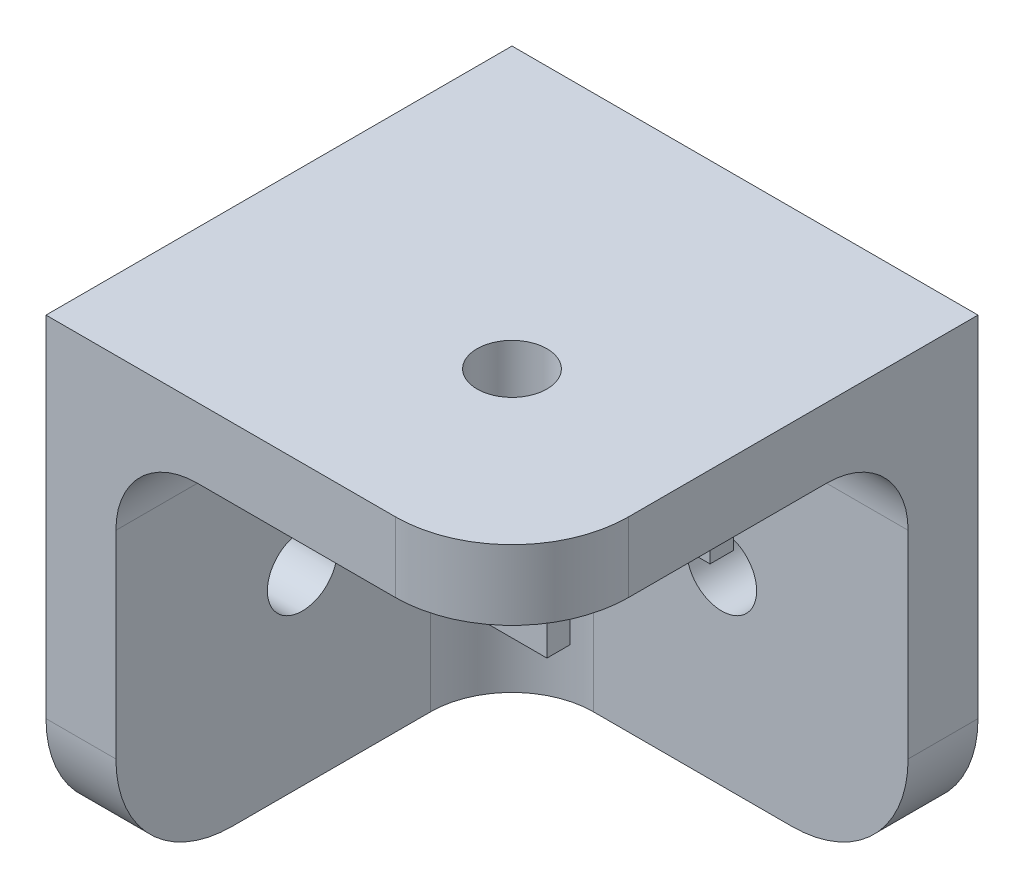
SolidWorks part; units mm, degrees
ref_plane "Front Plane" through (0, 0, 0) normal (0, 0, 1) x (1, 0, 0)
ref_plane "Top Plane" through (0, 0, 0) normal (0, 1, 0) x (1, 0, 0)
ref_plane "Right Plane" through (0, 0, 0) normal (1, 0, 0) x (0, 0, -1)
sketch "Sketch1" plane through (0, 0, 0) normal (0, 0, 1) x (1, 0, 0)
  line L1 (10, -10) -> (-10, -10)
  line L2 (10, -10) -> (10, 10)
  line L3 (10, 10) -> (-10, 10)
  line L4 (-10, -10) -> (-10, 10)
  line L5 (10, -10) -> (-10, 10) construction
  line L6 (10, 10) -> (-10, -10) construction
  point P0 (0, 0)
  dimension "D1" = 20
  dimension "D2" = 20
extrude "Base" add sketch "Sketch1" along normal mid plane 20
sketch "Sketch7" plane through (0, 0, 10) normal (0, 0, 1) x (1, 0, 0)
  line L1 (10, -10) -> (-7, -10)
  line L2 (10, -10) -> (10, 7)
  line L3 (10, 7) -> (-7, 7)
  line L4 (-7, -10) -> (-7, 7)
  dimension "D1" = 17
  dimension "D2" = 17
extrude "BaseCut" cut sketch "Sketch7" against normal blind 17
fillet "Fillet1" radius 3.5 3 edges at (1.5, 7, -7) (-7, -1.5, -7) (-7, 7, 1.5)
sketch "Sketch4" plane through (0, 0, 10) normal (0, 0, 1) x (1, 0, 0)
  line L2 (-10, 10) -> (-10, -10) construction
  line L3 (10, 10) -> (-10, 10) construction
  circle A0 centre (2, -2) radius 1.5
  dimension "D1" = 3
  dimension "D2" = 12
  dimension "D3" = 12
extrude "Cut-Extrude3" cut sketch "Sketch4" against normal through all
sketch "Sketch2" plane through (10, 0, 0) normal (1, 0, 0) x (0, 0, -1)
  line L2 (-10, 10) -> (10, 10) construction
  line L3 (10, -10) -> (10, 10) construction
  circle A0 centre (-2, -2) radius 1.5
  dimension "D1" = 3
  dimension "D2" = 12
  dimension "D3" = 12
extrude "Cut-Extrude1" cut sketch "Sketch2" against normal through all
sketch "Sketch3" plane through (0, 10, 0) normal (0, 1, 0) x (1, 0, 0)
  line L0 (-10, -10) -> (-10, 10) construction
  line L1 (10, 10) -> (-10, 10) construction
  circle A0 centre (2, -2) radius 1.5
  dimension "D1" = 3
  dimension "D2" = 12
  dimension "D3" = 12
extrude "Cut-Extrude2" cut sketch "Sketch3" against normal through all
sketch "Sketch8" plane through (0, 7, 0) normal (0, -1, 0) x (1, 0, 0)
  line L0 (2, 2) -> (-1.5276, 2) construction
  line L1 (7.5, 5) -> (-0.5, 5)
  line L2 (7.5, 6) -> (-0.9142, 6)
  line L3 (7.5, -1) -> (-0.5, -1)
  line L4 (-1.5, 4) -> (-1.5, 0)
  line L5 (-0.5, 5) -> (-1.5, 4)
  line L6 (-0.5, -1) -> (-1.5, 0)
  line L7 (-0.9142, 6) -> (-2.5, 4.4142)
  line L8 (-2.5, 4.4142) -> (-2.5, -0.4142)
  line L9 (-0.9142, -2) -> (-2.5, -0.4142)
  line L10 (7.5, -2) -> (-0.9142, -2)
  line L11 (7.5, 5) -> (7.5, 6)
  line L12 (7.5, -2) -> (7.5, -1)
  line L13 (10, -10) -> (-10, -10) construction
  line L14 (-10, 10) -> (-10, -10) construction
  point P1 (-1.5, -1)
  point P3 (-1.5, 5)
  dimension "D1" = 6
  dimension "D2" = 9
  dimension "D3" = 1
  dimension "D4" = 3.5
  dimension "D7" = 12
  dimension "D8" = 12
extrude "Boss-Extrude1" add sketch "Sketch8" along normal blind 3
fillet "Fillet2" radius 5 3 edges at (10, 8.5, 10) (10, -10, -8.5) (-8.5, -10, 10)
sketch "Sketch9" plane through (0, 0, -7) normal (0, 0, 1) x (1, 0, 0)
  line L0 (2, -2) -> (-0.2331, -2) construction
  line L1 (7.5, 1) -> (-0.5, 1)
  line L2 (7.5, 2) -> (-0.9142, 2)
  line L3 (7.5, -5) -> (-0.5, -5)
  line L4 (-1.5, 0) -> (-1.5, -4)
  line L5 (-0.5, 1) -> (-1.5, 0)
  line L6 (-0.5, -5) -> (-1.5, -4)
  line L7 (-0.9142, 2) -> (-2.5, 0.4142)
  line L8 (-2.5, 0.4142) -> (-2.5, -4.4142)
  line L9 (-0.9142, -6) -> (-2.5, -4.4142)
  line L10 (7.5, -6) -> (-0.9142, -6)
  line L11 (7.5, 1) -> (7.5, 2)
  line L12 (7.5, -6) -> (7.5, -5)
  line L15 (-10, -5) -> (-10, -10) construction
  line L16 (5, 10) -> (-10, 10) construction
  point P1 (-1.5, -5)
  point P3 (-1.5, 1)
  dimension "D1" = 6
  dimension "D2" = 9
  dimension "D3" = 1
  dimension "D4" = 3.5
  dimension "D7" = 12
  dimension "D8" = 12
extrude "Boss-Extrude2" [suppressed] add sketch "Sketch9" along normal blind 3
